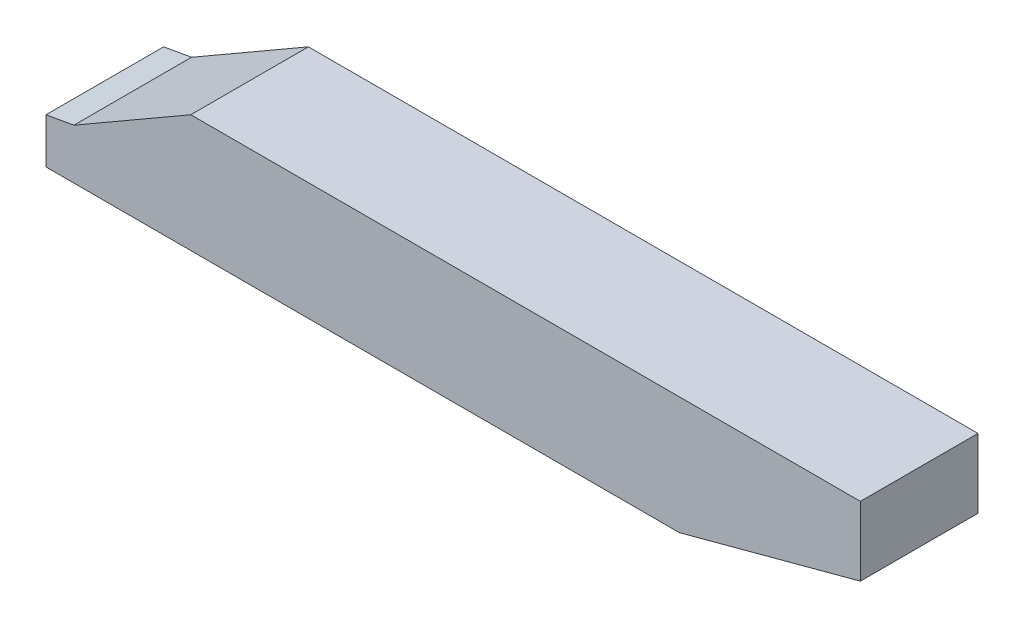
SolidWorks part; units mm, degrees
ref_plane "Front Plane" through (0, 0, 0) normal (0, 0, 1) x (1, 0, 0)
ref_plane "Top Plane" through (0, 0, 0) normal (0, 1, 0) x (1, 0, 0)
ref_plane "Right Plane" through (0, 0, 0) normal (1, 0, 0) x (0, 0, -1)
sketch "Sketch1" plane through (0, 0, 0) normal (0, 0, 1) x (1, 0, 0)
  line L0 (0, 0) -> (0, 50)
  line L5 (0, 50) -> (30.8612, 55.4417)
  line L6 (30.8612, 55.4417) -> (160, 130)
  line L7 (160, 130) -> (900, 130)
  line L8 (900, 130) -> (900, 53.5898)
  line L12 (700, 0) -> (0, 0)
  line L14 (700, 0) -> (900, 53.5898)
  line L15 (700, 0) -> (975.2284, 0) construction
  line L16 (500, 223.146) -> (500, -84.7981) construction
  dimension "D1" = 50
  dimension "D2" = 10
  dimension "D3" = 160
  dimension "0" = 700
  dimension "D4" = 130
  dimension "D5" = 900
  dimension "D6" = 30
  dimension "D7" = 15
  dimension "D8" = 31.3372
  dimension "D9" = 500
  dimension "D10" = 200
  dimension "D11" = 76.4102
extrude "Boss-Extrude1" add sketch "Sketch1" along normal mid plane 130
shell "Shell1" thickness 3
sketch "Sketch2" plane through (0, 0, 0) normal (-1, 0, 0) x (0, 0, 1)
  line L0 (65, 50) -> (-65, 50) construction
  line L2 (0, 50) -> (0, 0) construction
  circle A0 centre (0, 25) radius 15
  point P8 (0, 25)
  dimension "D1" = 30
extrude "Cut-Extrude1" cut sketch "Sketch2" against normal up to next
